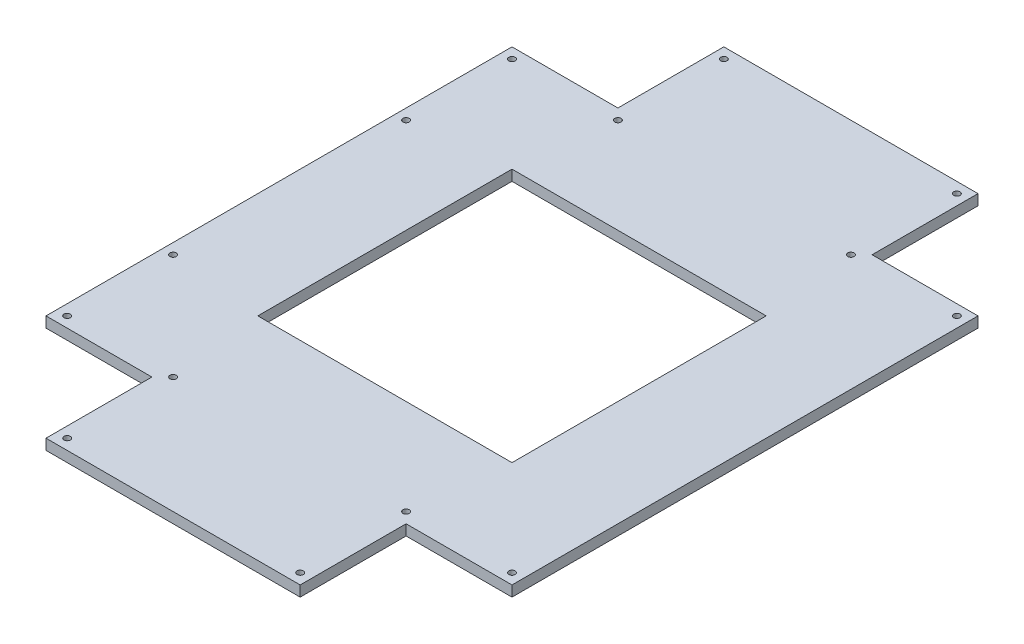
SolidWorks part; units mm, degrees
ref_plane "Plan de face" through (0, 0, 0) normal (0, 0, 1) x (1, 0, 0)
ref_plane "Plan de dessus" through (0, 0, 0) normal (0, 1, 0) x (1, 0, 0)
ref_plane "Plan de droite" through (0, 0, 0) normal (1, 0, 0) x (0, 0, -1)
sketch "Esquisse1" plane through (0, 0, 0) normal (0, 1, 0) x (1, 0, 0)
  line L0 (-60, 110) -> (-60, 160)
  line L1 (110, -110) -> (60, -110)
  line L2 (110, -110) -> (110, 110)
  line L3 (110, 110) -> (60, 110)
  line L4 (-110, -110) -> (-110, 0)
  line L5 (110, -110) -> (-110, 110) construction
  line L6 (110, 110) -> (-110, -110) construction
  line L7 (-60, 160) -> (60, 160)
  line L8 (60, 160) -> (60, 110)
  line L9 (0, 160) -> (0, -160) construction
  line L10 (-110, 0) -> (110, 0) construction
  line L11 (-105, -105) -> (-105, -50) construction
  line L12 (-55, -105) -> (-55, -160) construction
  line L13 (-60, 110) -> (-110, 110)
  line L14 (60, -160) -> (60, -110)
  line L15 (-60, -160) -> (60, -160)
  line L16 (-60, -110) -> (-60, -160)
  line L17 (-60, -110) -> (-110, -110)
  line L28 (-110, 0) -> (-110, 110)
  line L33 (-105, -105) -> (105, -105) construction
  line L34 (105, -105) -> (105, 0) construction
  line L35 (60, -60) -> (-60, -60)
  line L36 (60, -60) -> (60, 60)
  line L37 (60, 60) -> (-60, 60)
  line L38 (-60, -60) -> (-60, 60)
  line L39 (60, -60) -> (-60, 60) construction
  line L40 (60, 60) -> (-60, -60) construction
  circle A0 centre (-105, -105) radius 1.5
  circle A1 centre (-105, -55) radius 1.5
  circle A2 centre (-55, -105) radius 1.5
  circle A5 centre (-5, -105) radius 1.5 [skipped]
  circle A6 centre (45, -105) radius 1.5 [skipped]
  circle A7 centre (-55, -155) radius 1.5
  circle A8 centre (-55, 155) radius 1.5
  circle A9 centre (-55, 105) radius 1.5
  circle A10 centre (-105, 105) radius 1.5
  circle A11 centre (-105, 55) radius 1.5
  circle A12 centre (55, -155) radius 1.5
  circle A13 centre (55, -105) radius 1.5
  circle A14 centre (105, -105) radius 1.5
  circle A15 centre (105, 105) radius 1.5
  circle A16 centre (55, 105) radius 1.5
  circle A17 centre (55, 155) radius 1.5
  point P0 (0, 0)
  point P23 (0, 0)
  point P24 (0, 0)
  point P33 (0, 0)
  dimension "D4" = 3
  dimension "D6" = 50
  dimension "D14" = 5
  dimension "D16" = 5
  dimension "D1" = 220
  dimension "D2" = 50
  dimension "D3" = 50
  dimension "D5" = 5
  dimension "D7" = 120
  dimension "D13" = 2
  dimension "D15" = 4
  dimension "D17" = 2
extrude "Boss.-Extru.1" add sketch "Esquisse1" along normal blind 5
